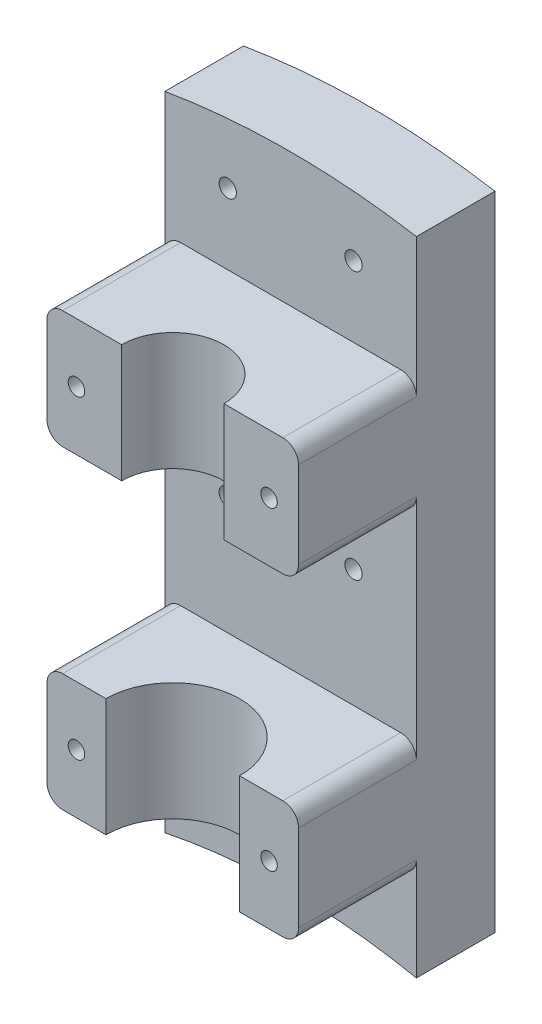
SolidWorks part; units mm, degrees
note: The reader was unsure of these and kept them because the rebuilt part matched: shared geometry of "Sketch1<9>".
ref_plane "Front Plane" through (0, 0, 0) normal (0, 0, 1) x (1, 0, 0)
ref_plane "Top Plane" through (0, 0, 0) normal (0, 1, 0) x (1, 0, 0)
ref_plane "Right Plane" through (0, 0, 0) normal (1, 0, 0) x (0, 0, -1)
sketch "Sketch1" plane through (0, 0, 0) normal (0, 0, 1) x (1, 0, 0)
  line L0 (-18.6299, -7.8695) -> (-18.6299, 64.1305) construction
  line L1 (-18.6299, 56.1305) -> (-10.6299, 56.1305) construction
  line L5 (-34.6299, 7.1305) -> (-2.6299, 7.1305) construction
  line L6 (-34.6299, 32.1305) -> (-2.6299, 32.1305) construction
  line L8 (-34.6299, 47.1305) -> (-2.6299, 47.1305) construction
  line L9 (-18.6299, 22.1305) -> (-10.6299, 22.1305) construction
  line L10 (-34.6299, -7.8695) -> (-34.6299, -18.8955)
  line L13 (-2.6299, -7.8695) -> (-2.6299, -18.8955)
  line L18 (-34.6299, 62.7878) -> (-34.6299, -7.8695)
  line L19 (-2.6299, 62.7878) -> (-2.6299, -7.8695)
  line L20 (-34.6299, -7.8695) -> (-2.6299, -7.8695)
  circle A16 centre (-10.6299, 56.1305) radius 1.1
  circle A18 centre (-26.6299, 56.1305) radius 1.1
  arc A19 (-2.6299, 62.7878) -> (-34.6299, 62.7878) centre (-18.6299, -31.8695) ccw
  arc A20 (-2.6299, 46.5142) -> (-34.6299, 46.5142) centre (-18.6299, -31.8695) ccw
  arc A21 (-2.6299, 28.7878) -> (-34.6299, 28.7878) centre (-18.6299, -65.8695) ccw
  circle A22 centre (-10.6299, 22.1305) radius 1.1
  arc A23 (-2.6299, 12.5142) -> (-34.6299, 12.5142) centre (-18.6299, -65.8695) ccw
  circle A24 centre (-26.6299, 22.1305) radius 1.1
  circle A25 centre (-26.6299, -9.2791) radius 1.1
  arc A26 (-2.6299, -2.6219) -> (-34.6299, -2.6219) centre (-18.6299, -97.2791) ccw
  circle A27 centre (-10.6299, -9.2791) radius 1.1
  arc A28 (-2.6299, -18.8955) -> (-34.6299, -18.8955) centre (-18.6299, -97.2791) ccw
  point P12 (-18.6299, 64.1305)
  point P19 (-18.6299, 22.1305)
  dimension "D1" = 160
  dimension "D2" = 2.2
  dimension "D3" = 8
  dimension "D4" = 72
  dimension "D5" = 192
  dimension "D6" = 32
  dimension "D7" = 8
  dimension "D8" = 15
  dimension "D10" = 15
  dimension "D11" = 10
  dimension "D9" = 25
extrude "Boss-Extrude7" add sketch "Sketch1" along normal blind 10 contours A28 L13 L20 L10 A27 A25
extrude "Cut-Extrude4" cut sketch "Sketch1<9>" along normal through all both and the other way through all
sketch "Sketch1<9>" plane through (0, 0, 0) normal (0, 0, 1) x (1, 0, 0) same geometry as "Sketch1"
sketch "Sketch6" plane through (0, 0, 10) normal (0, 0, 1) x (1, 0, 0)
  line L0 (-34.6299, 7.1305) -> (-2.6299, 7.1305)
  line L1 (-34.6299, 32.1305) -> (-2.6299, 32.1305)
  line L2 (-34.6299, 47.1305) -> (-2.6299, 47.1305)
  line L3 (-34.6299, 62.7878) -> (-34.6299, -18.8955) construction
  line L4 (-2.6299, 62.7878) -> (-2.6299, -18.8955) construction
  line L9 (-34.6299, 62.7878) -> (-34.6299, -7.8695)
  line L10 (-34.6299, -7.8695) -> (-2.6299, -7.8695)
  line L11 (-2.6299, -7.8695) -> (-2.6299, 62.7878)
  arc A2 (-2.6299, 62.7878) -> (-34.6299, 62.7878) centre (-18.6299, -31.8695) ccw
  dimension "D2" = 15
  dimension "D3" = 15
  dimension "D4" = 25
extrude "Boss-Extrude8" add sketch "Sketch6" along normal blind 30
sketch "Sketch7" plane through (0, 47.1305, 0) normal (0, 1, 0) x (1, 0, 0)
  line L0 (-18.6299, -10) -> (-18.6299, -40) construction
  line L1 (-18.6299, -25) -> (-34.6299, -25) construction
  line L2 (-34.6299, -25) -> (-2.6299, -25) construction
  line L3 (-34.6299, -10) -> (-34.6299, -40) construction
  line L4 (-2.6299, -10) -> (-34.6299, -10)
  line L5 (-2.6299, -10) -> (-34.6299, -10)
  line L6 (-34.6299, -40) -> (-2.6299, -40)
  line L7 (-34.6299, -10) -> (-34.6299, -40)
  line L10 (-34.6299, -40) -> (-2.6299, -40)
  line L12 (-2.6299, -10) -> (-2.6299, -40) construction
  line L13 (-34.6299, -10) -> (-34.6299, -25)
  line L14 (-34.6299, -25) -> (-34.6299, -40)
  line L15 (-2.6299, -10) -> (-2.6299, -25)
  line L16 (-2.6299, -25) -> (-2.6299, -40)
  line L17 (-34.6299, -25) -> (-25.1299, -25)
  line L18 (-25.1299, -25) -> (-2.6299, -25)
  line L23 (-34.6299, -10) -> (-34.6299, -40)
  line L24 (-2.6299, -40) -> (-2.6299, -10)
  line L25 (-2.6299, -40) -> (-2.6299, -10)
  circle A0 centre (-18.6299, -25) radius 6.5
  dimension "D2" = 13
  dimension "D1" = 0
sketch "Sketch8" plane through (0, 7.1305, 0) normal (0, 1, 0) x (1, 0, 0)
  line L0 (-18.6299, -10) -> (-18.6299, -40) construction
  line L1 (-34.6299, -25) -> (-2.6299, -25) construction
  line L2 (-27.1299, -25) -> (-34.6299, -25)
  line L3 (-10.1299, -25) -> (-2.6299, -25)
  line L4 (-2.6299, -10) -> (-34.6299, -10)
  line L5 (-2.6299, -10) -> (-34.6299, -10)
  line L6 (-34.6299, -40) -> (-2.6299, -40)
  line L7 (-34.6299, -10) -> (-34.6299, -40)
  line L10 (-34.6299, -40) -> (-2.6299, -40)
  line L12 (-34.6299, -10) -> (-34.6299, -40)
  line L13 (-2.6299, -40) -> (-2.6299, -10)
  line L14 (-34.6299, -10) -> (-34.6299, -25)
  line L15 (-2.6299, -25) -> (-2.6299, -10)
  line L16 (-34.6299, -10) -> (-34.6299, -25) construction
  line L17 (-34.6299, -25) -> (-34.6299, -40) construction
  line L18 (-34.6299, -40) -> (-2.6299, -40) construction
  line L19 (-2.6299, -10) -> (-2.6299, -25) construction
  line L20 (-2.6299, -25) -> (-2.6299, -40) construction
  line L25 (-34.6299, -10) -> (-34.6299, -40)
  line L26 (-2.6299, -40) -> (-2.6299, -10)
  line L27 (-2.6299, -40) -> (-2.6299, -10)
  circle A0 centre (-18.6299, -25) radius 8.5
  dimension "D2" = 17
  dimension "D1" = 0
extrude "Cut-Extrude5" cut sketch "Sketch7" against normal blind 16
extrude "Cut-Extrude6" cut sketch "Sketch8" against normal blind 22
sketch "Sketch10" plane through (0, 0, 25) normal (0, 0, 1) x (1, 0, 0)
  line L0 (-27.1299, -7.8695) -> (-27.1299, 7.1305) construction
  line L1 (-27.1299, 7.1305) -> (-34.6299, 7.1305) construction
  line L2 (-34.6299, 7.1305) -> (-34.6299, -7.8695) construction
  line L4 (-34.6299, 32.1305) -> (-25.1299, 32.1305)
  line L5 (-25.1299, 32.1305) -> (-25.1299, 47.1305)
  line L6 (-25.1299, 47.1305) -> (-34.6299, 47.1305)
  line L7 (-34.6299, 47.1305) -> (-34.6299, 32.1305)
  line L8 (-34.6299, 32.1305) -> (-25.1299, 32.1305)
  line L9 (-25.1299, 32.1305) -> (-25.1299, 47.1305)
  line L10 (-25.1299, 47.1305) -> (-34.6299, 47.1305)
  line L11 (-34.6299, 47.1305) -> (-34.6299, 32.1305)
  line L13 (-2.6299, -7.8695) -> (-2.6299, 7.1305) construction
  line L14 (-2.6299, 7.1305) -> (-10.1299, 7.1305) construction
  line L15 (-10.1299, 7.1305) -> (-10.1299, -7.8695) construction
  line L16 (-12.1299, 32.1305) -> (-2.6299, 32.1305) construction
  line L17 (-2.6299, 32.1305) -> (-2.6299, 47.1305) construction
  line L18 (-2.6299, 47.1305) -> (-12.1299, 47.1305) construction
  line L19 (-12.1299, 47.1305) -> (-12.1299, 32.1305) construction
  line L20 (-27.1299, -7.8695) -> (-27.1299, 7.1305)
  line L21 (-27.1299, 7.1305) -> (-34.6299, 7.1305)
  line L22 (-34.6299, 7.1305) -> (-34.6299, -7.8695)
  line L23 (-34.6299, -7.8695) -> (-27.1299, -7.8695)
  line L24 (-10.1299, -7.8695) -> (-2.6299, -7.8695)
  line L25 (-2.6299, -7.8695) -> (-2.6299, 7.1305)
  line L26 (-2.6299, 7.1305) -> (-10.1299, 7.1305)
  line L27 (-10.1299, 7.1305) -> (-10.1299, -7.8695)
  line L28 (-12.1299, 32.1305) -> (-2.6299, 32.1305)
  line L29 (-2.6299, 32.1305) -> (-2.6299, 47.1305)
  line L30 (-2.6299, 47.1305) -> (-12.1299, 47.1305)
  line L31 (-12.1299, 47.1305) -> (-12.1299, 32.1305)
  line L32 (-34.6299, 47.1305) -> (-2.6299, 47.1305) construction
  line L33 (-2.6299, -7.8695) -> (-34.6299, -7.8695) construction
  line L34 (-34.6299, 47.1305) -> (-18.6299, 47.1305) construction
  line L35 (-18.6299, 47.1305) -> (-18.6299, -7.8695) construction
  line L36 (-18.6299, -7.8695) -> (-18.6299, 19.6305) construction
  line L37 (-18.6299, 19.6305) -> (-34.6299, 19.6305) construction
  line L39 (-30.8799, -7.8695) -> (-30.8799, 7.1305) construction
  circle A0 centre (-30.8799, -0.3695) radius 1.05
  circle A1 centre (-30.8799, 39.6305) radius 1.05
  circle A2 centre (-6.3799, -0.3695) radius 1.05
  circle A3 centre (-6.3799, 39.6305) radius 1.05
  point P32 (0, 0)
  point P33 (0, 0)
  point P34 (0, 0)
  dimension "D2" = 2.1
  dimension "D1" = 0
extrude "Cut-Extrude7" cut sketch "Sketch10" against normal blind 10 contours A1 | A3 | A2 | A0
fillet "Fillet1" radius 2 8 edges at (-34.6299, 7.1305, 17.5) (-2.6299, 7.1305, 17.5) (-34.6299, 47.1305, 17.5) (-2.6299, 47.1305, 17.5) (-34.6299, 32.1305, 17.5) (-2.6299, 32.1305, 17.5) (-2.6299, -7.8695, 17.5) (-34.6299, -7.8695, 17.5)
